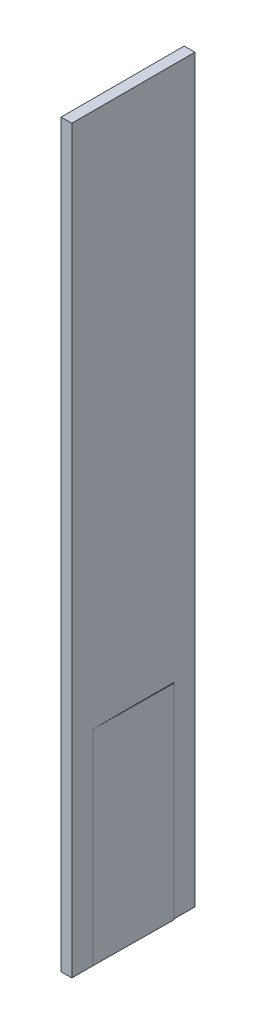
SolidWorks part; units mm, degrees
material "6061-T6 (SS)"
ref_plane "Front" through (0, 0, 0) normal (0, 0, 1) x (1, 0, 0)
ref_plane "Top" through (0, 0, 0) normal (0, 1, 0) x (1, 0, 0)
ref_plane "Right" through (0, 0, 0) normal (1, 0, 0) x (0, 0, -1)
sketch "Sketch1" plane through (0, 0, 0) normal (0, 1, 0) x (1, 0, 0)
  line L1 (-50.8, 584.2) -> (50.8, 584.2)
  line L2 (-50.8, 584.2) -> (-50.8, -584.2)
  line L3 (-50.8, -584.2) -> (50.8, -584.2)
  line L4 (50.8, 584.2) -> (50.8, -584.2)
  line L5 (-50.8, 584.2) -> (50.8, -584.2) construction
  line L6 (-50.8, -584.2) -> (50.8, 584.2) construction
  point P0 (0, 0)
  dimension "D1" = 1168.4
  dimension "D2" = 101.6
extrude "Boss-Extrude1" add sketch "Sketch1" along normal blind 7023.1
sketch "Sketch2" plane through (50.8, 0, 0) normal (1, 0, 0) x (0, 0, -1)
  line L0 (584.2, 7023.1) -> (584.2, 0) construction
  line L1 (584.2, 0) -> (431.8, 0)
  line L2 (584.2, 0) -> (584.2, 2286)
  line L3 (584.2, 2286) -> (431.8, 2286)
  line L4 (431.8, 0) -> (431.8, 2286)
  line L6 (-584.2, 0) -> (584.2, 0) construction
  dimension "D1" = 152.4
  dimension "D2" = 2286
extrude "Cut-Extrude1" [suppressed] cut sketch "Sketch2" against normal through all
sketch "Sketch3" plane through (50.8, 0, 0) normal (1, 0, 0) x (0, 0, -1)
  line L2 (-381, 1944.6548) -> (-381, 0)
  line L4 (377.825, 0) -> (812.8, 0) construction
  line L5 (381, 0) -> (-381, 0)
  line L6 (584.2, 7023.1) -> (584.2, 0) construction
  line L12 (381, 1944.6548) -> (381, 0)
  line L13 (-381, 1944.6548) -> (381, 1944.6548)
  dimension "D2" = 1944.6548
  dimension "D1" = 762
  dimension "D3" = 203.2
extrude "Cut-Extrude2" cut sketch "Sketch3" against normal through all
sketch "Sketch4" [suppressed] plane through (-76.2, 0, 0) normal (-1, 0, 0) x (0, 0, 1)
  line L0 (-584.2, 6400.8) -> (584.2, 6400.8) construction
  line L1 (584.2, 6400.8) -> (584.2, 0) construction
  circle A0 centre (177.8, 5994.4) radius 152.4
  dimension "D1" = 304.8
  dimension "D2" = 406.4
  dimension "D3" = 406.4
extrude "Cut-Extrude3" [suppressed] cut sketch "Sketch4" against normal through all and the other way through all
sketch "Sketch5" [suppressed] plane through (-76.2, 0, 0) normal (-1, 0, 0) x (0, 0, 1)
  line L0 (584.2, 6400.8) -> (584.2, 0) construction
  line L1 (-584.2, 0) -> (584.2, 0) construction
  circle A0 centre (177.8, 406.4) radius 152.4
  dimension "D1" = 304.8
  dimension "D2" = 406.4
  dimension "D3" = 406.4
extrude "Cut-Extrude4" [suppressed] cut sketch "Sketch5" against normal through all
sketch "Sketch6" [suppressed] plane through (50.8, 0, 0) normal (1, 0, 0) x (0, 0, -1)
  line L0 (-584.2, 7023.1) -> (-584.2, 0) construction
  line L1 (584.2, 0) -> (-584.2, 0)
  line L2 (584.2, 0) -> (584.2, 4267.2)
  line L3 (584.2, 4267.2) -> (-584.2, 4267.2)
  line L4 (-584.2, 0) -> (-584.2, 4267.2)
  dimension "D1" = 4267.2
extrude "Cut-Extrude5" [suppressed] cut sketch "Sketch6" against normal through all
sketch "Sketch7" [suppressed] plane through (50.8, 0, 0) normal (1, 0, 0) x (0, 0, -1)
  line L1 (-584.2, 0) -> (215.9, 0)
  line L2 (-584.2, 0) -> (-584.2, 4267.2)
  line L3 (-584.2, 4267.2) -> (215.9, 4267.2)
  line L4 (215.9, 0) -> (215.9, 4267.2)
  dimension "D1" = 4267.2
  dimension "D2" = 800.1
extrude "Cut-Extrude6" [suppressed] cut sketch "Sketch7" against normal through all
sketch "Sketch8" plane through (0, 1944.6548, 0) normal (0, -1, 0) x (1, 0, 0)
  line L0 (50.8, 381) -> (57.4496, -380.971)
  line L1 (57.4496, -380.971) -> (-31.447, -381.7468)
  line L2 (-31.447, -381.7468) -> (-38.0966, 380.2242)
  line L3 (-38.0966, 380.2242) -> (50.8, 381)
  line L4 (50.8, -381) -> (50.8, 381) construction
  dimension "D1" = 762
  dimension "D2" = 88.9
  dimension "D3" = 0.5
extrude "Boss-Extrude2" add sketch "Sketch8" along normal up to surface (1944.6548 mm away) separate body up to face at (0, 0, 482.6)
